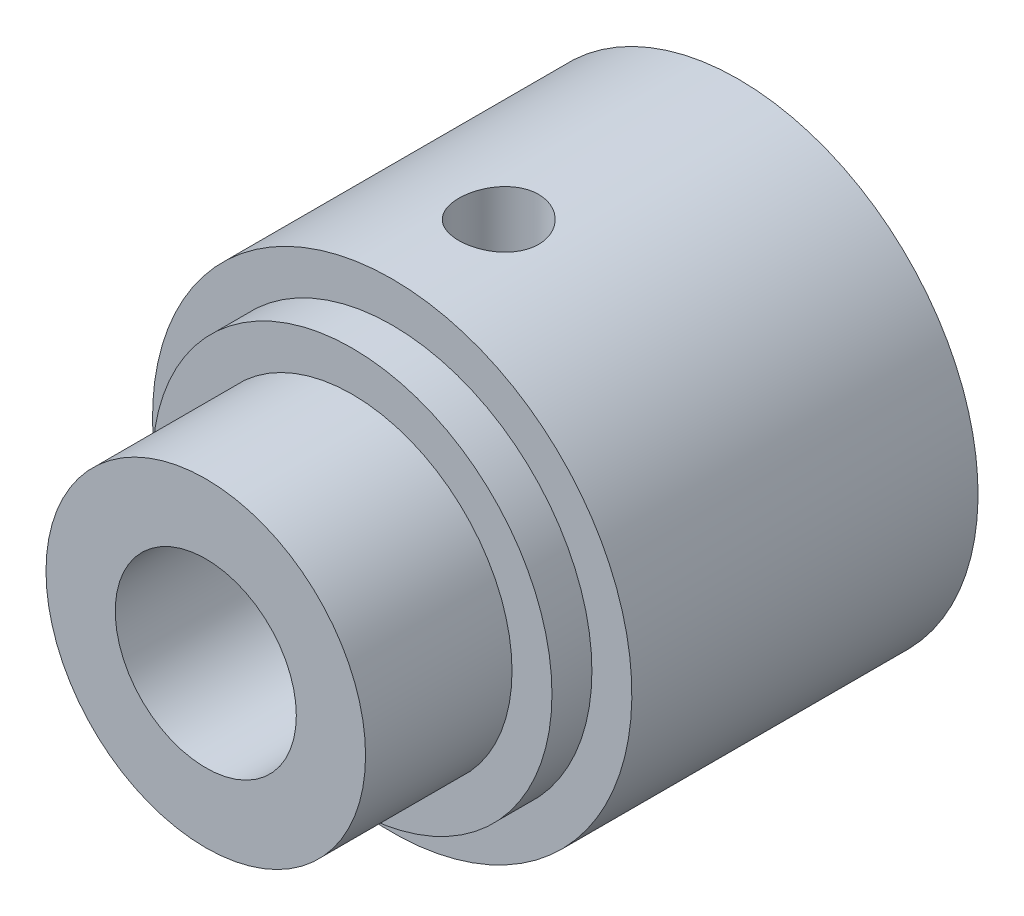
SolidWorks part; units mm, degrees
material "1060 Alloy"
ref_plane "Front Plane" through (0, 0, 0) normal (0, 0, 1) x (1, 0, 0)
ref_plane "Top Plane" through (0, 0, 0) normal (0, 1, 0) x (1, 0, 0)
ref_plane "Right Plane" through (0, 0, 0) normal (1, 0, 0) x (0, 0, -1)
sketch "Sketch1" plane through (0, 0, 0) normal (1, 0, 0) x (0, 0, -1)
  line L0 (0, 0) -> (0, 6)
  line L1 (5.5, 6) -> (5.5, 7.5)
  line L2 (5.5, 7.5) -> (7, 7.5)
  line L3 (0, 6) -> (5.5, 6)
  line L4 (7, 7.5) -> (7, 9)
  line L5 (7, 9) -> (20, 9)
  line L6 (6.9764, 0) -> (9.5, 4.2)
  line L7 (6.9764, 0) -> (0, 0)
  line L8 (9.5, 4.2) -> (20, 4.2)
  line L9 (20, 4.2) -> (20, 9)
  dimension "D1" = 1.5
  dimension "D2" = 1.5
  dimension "D3" = 1.5
  dimension "D4" = 6
  dimension "D5" = 13
  dimension "D6" = 7
  dimension "D7" = 4.2
  dimension "D8" = 2.5
  dimension "D9" = 121
revolve "Revolve1" add sketch "Sketch1" angle 360 about L7
sketch "Sketch2" plane through (0, 0, 0) normal (0, 1, 0) x (1, 0, 0)
  line L1 (-9, 7) -> (9, 7) construction
  circle A0 centre (0, 11) radius 1.5
  dimension "D2" = 3
  dimension "D1" = 4
extrude "Cut-Extrude1" cut sketch "Sketch2" against normal up to next and the other way up to next
hole_wizard "Tap Drill for M8x1.25 Tap2" positions "Sketch4" profile "Sketch5" hole size "M8x1.25" standard "ANSI Metric"
sketch "Sketch4" plane through (0, 0, 0) normal (0, 0, 1) x (1, 0, 0)
  point P0 (0, 0)
sketch "Sketch5" plane through (0, 0, 0) normal (1, 0, 0) x (0, -1, 0)
  line L0 (0, 0) -> (0, 12.0429)
  line L1 (0, 12.0429) -> (3.4, 10)
  line L2 (3.4, 10) -> (3.4, 0)
  line L5 (3.4, 0) -> (0, 0)
  line L10 (0, 12.0429) -> (-3.4, 10) construction
  line L11 (0, -6.35) -> (0, 107.95) construction
  dimension "Hole Dia." = 6.8
  dimension "Hole Depth" = 10
  dimension "Drill Angle" = 118
